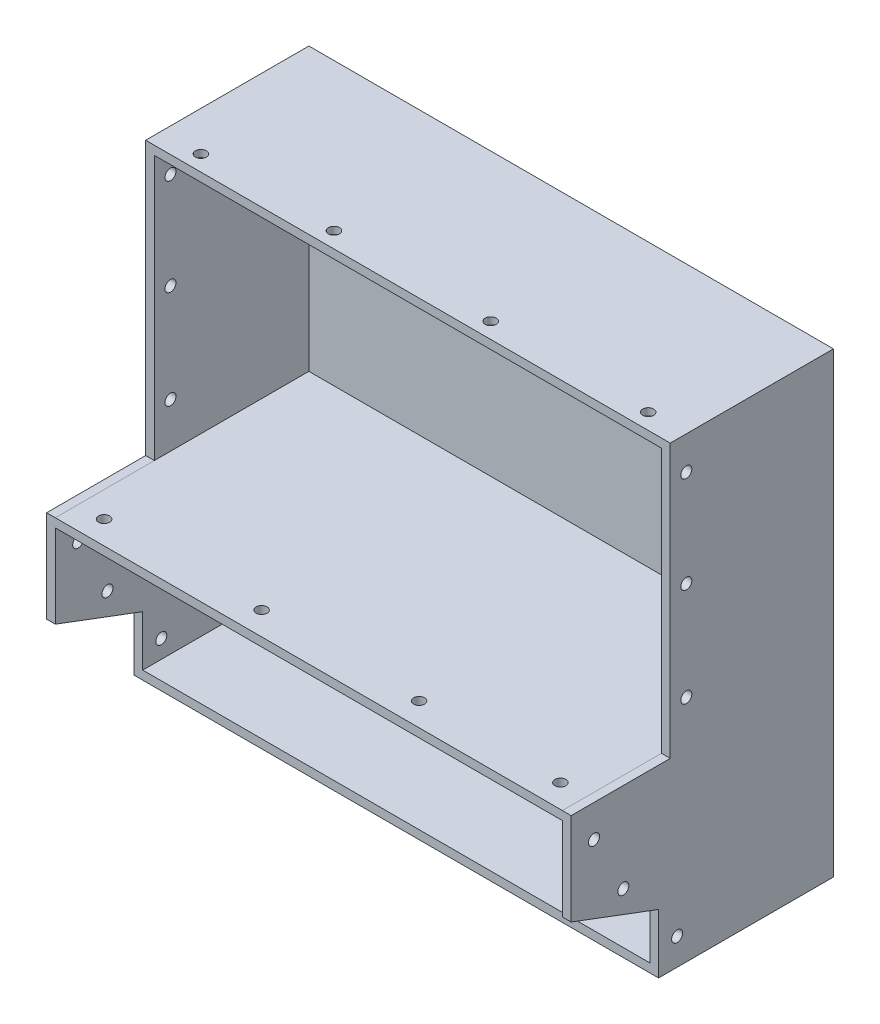
SolidWorks part; units mm, degrees
material "Custom Plastic"
ref_plane "X-Y Datum" through (0, 0, 0) normal (0, 0, 1) x (1, 0, 0)
ref_plane "X-Z Datum" through (0, 0, 0) normal (0, 1, 0) x (1, 0, 0)
ref_plane "Y-Z Datum" through (0, 0, 0) normal (1, 0, 0) x (0, 0, -1)
sketch "Sketch1" plane through (0, 0, 0) normal (0, 0, 1) x (1, 0, 0)
  line L1 (-95.25, -83.058) -> (95.25, -83.058)
  line L2 (-95.25, -83.058) -> (-95.25, 83.058)
  line L3 (-95.25, 83.058) -> (95.25, 83.058)
  line L4 (95.25, -83.058) -> (95.25, 83.058)
  line L5 (-95.25, -83.058) -> (95.25, 83.058) construction
  line L6 (-95.25, 83.058) -> (95.25, -83.058) construction
  point P0 (0, 0)
  dimension "D1" = 166.116
  dimension "D2" = 190.5
extrude "Boss-Extrude1" add sketch "Sketch1" along normal blind 95.25
sketch "Sketch3" plane through (0, 0, 95.25) normal (0, 0, 1) x (1, 0, 0)
  line L0 (-92.075, -49.9618) -> (92.075, -49.9618)
  line L1 (92.075, -61.8913) -> (95.25, -61.8913)
  line L2 (-92.075, -61.8913) -> (92.075, -61.8913)
  line L3 (95.25, -83.058) -> (95.25, 83.058) construction
  line L4 (-92.075, -61.8913) -> (-92.075, -79.883)
  line L5 (-95.25, -49.9618) -> (-95.25, -61.8913)
  line L6 (92.075, -61.8913) -> (92.075, -79.883)
  line L7 (-95.25, 83.058) -> (-95.25, -83.058) construction
  line L8 (-122.0928, 3.2687) -> (-122.1486, 3.2687)
  line L9 (92.075, -79.883) -> (76.2531, -79.883)
  line L13 (-95.25, 32.8917) -> (-92.075, 32.8917)
  line L15 (-122.0786, -16.0951) -> (-122.1486, -16.0951)
  line L17 (95.25, -49.9618) -> (92.075, -49.9618)
  line L18 (-92.075, -79.883) -> (76.2531, -79.883)
  line L21 (-92.075, -49.9618) -> (-95.25, -49.9618)
  line L23 (-81.0858, 79.883) -> (83.8833, 79.883)
  line L25 (-81.0858, 79.883) -> (-92.075, 79.883)
  line L26 (-92.075, 79.883) -> (-92.075, -16.0951)
  line L28 (95.25, 48.6627) -> (92.075, 48.6627)
  line L30 (83.8833, 79.883) -> (92.075, 79.883)
  line L31 (92.075, 79.883) -> (92.075, -16.0951)
  line L33 (-92.075, -16.0951) -> (92.075, -16.0951)
  line L34 (95.25, -49.9618) -> (95.25, -61.8913)
  line L35 (-95.25, -61.8913) -> (-92.075, -61.8913)
extrude "Cut-Extrude1" cut sketch "Sketch3" against normal blind 92.075 contours L23 region at (0, 31.8939, 95.25)
sketch "Sketch15" plane through (0, 0, 95.25) normal (0, 0, 1) x (1, 0, 0)
  line L1 (-95.25, 83.058) -> (-95.25, -83.058) construction
  line L3 (95.25, -83.058) -> (95.25, 83.058) construction
  line L4 (95.25, -16.1093) -> (95.25, 83.058)
  line L5 (95.25, 83.058) -> (-95.25, 83.058)
  line L6 (-95.25, 83.058) -> (-95.25, -16.1093)
  line L10 (95.25, -16.1093) -> (92.075, -16.0951)
  line L11 (92.075, -16.0951) -> (92.075, 79.883)
  line L12 (92.075, 79.883) -> (-92.075, 79.883)
  line L13 (-92.075, 79.883) -> (-92.075, -16.0951)
  line L14 (-92.075, -16.0951) -> (92.075, -16.0951) construction
  line L15 (-92.075, 79.883) -> (-92.075, -16.0951) construction
  line L16 (-95.25, -16.1093) -> (-92.075, -16.0951)
extrude "Cut-Extrude5" cut sketch "Sketch15" against normal blind 35.9842
sketch "Sketch17" plane through (0, 0, 95.25) normal (0, 0, 1) x (1, 0, 0)
  line L0 (-95.25, -49.5836) -> (-95.25, -83.058)
  line L2 (-95.25, -83.058) -> (95.25, -83.058)
  line L3 (-95.25, -16.1093) -> (-95.25, -83.058) construction
  line L4 (95.25, -83.058) -> (95.25, -16.1093) construction
  line L5 (95.25, -83.058) -> (95.25, -49.5836)
  line L6 (-95.25, -49.5836) -> (95.25, -49.5836)
extrude "Cut-Extrude6" cut sketch "Sketch17" against normal blind 31.75
sketch "Sketch18" plane through (-95.25, 0, 0) normal (-1, 0, 0) x (0, 0, 1)
  line L0 (63.5, -49.5836) -> (63.5, -61.5061)
  line L1 (63.5, -49.5836) -> (63.5, -83.058) construction
  line L2 (63.5, -61.5061) -> (95.25, -49.5836)
  line L3 (95.25, -49.5836) -> (63.5, -49.5836)
extrude "Boss-Extrude8" add sketch "Sketch18" against normal blind 190.5
sketch "Sketch19" plane through (0, 0, 95.25) normal (0, 0, 1) x (1, 0, 0)
  line L0 (-92.075, -19.2701) -> (-92.075, -49.5836)
  line L2 (95.25, -49.5836) -> (-95.25, -49.5836) construction
  line L4 (92.075, -19.2701) -> (92.075, -49.5836)
  line L6 (92.075, -49.5836) -> (-92.075, -49.5836)
  line L8 (-92.075, -19.2701) -> (92.075, -19.2701)
extrude "Cut-Extrude7" cut sketch "Sketch19" against normal blind 92.075
sketch "Sketch20" plane through (0, -74.8032, 28.0894) normal (0, -0.9362, 0.3515) x (1, 0, 0)
  line L2 (-92.075, -3.8019) -> (-92.075, 82.3961) construction
  line L4 (-92.075, 71.7396) -> (92.075, 71.7396) construction
  line L6 (-92.075, 71.7396) -> (92.075, 71.7396)
  line L12 (92.075, -3.8019) -> (92.075, 82.3961) construction
  line L13 (95.25, 71.7396) -> (92.075, 71.7396) construction
  line L15 (-92.075, 71.7396) -> (-92.075, 37.8249)
  line L16 (95.25, 37.8249) -> (-95.25, 37.8249) construction
  line L17 (92.075, 71.7396) -> (92.075, 37.8249)
  line L18 (92.075, 37.8249) -> (-92.075, 37.8249)
extrude "Cut-Extrude8" cut sketch "Sketch20" against normal blind 13.175
sketch "Sketch21" plane through (0, 0, 63.5) normal (0, 0, 1) x (1, 0, 0)
  line L0 (-92.075, -61.5061) -> (-92.075, -49.5836)
  line L2 (-92.075, -49.5836) -> (92.075, -49.5836)
  line L4 (92.075, -49.5836) -> (92.075, -61.5061)
  line L6 (-92.075, -61.5061) -> (-92.075, -79.883)
  line L7 (-92.075, -79.883) -> (92.075, -79.883)
  line L8 (92.075, -79.883) -> (92.075, -61.5061)
extrude "Cut-Extrude9" cut sketch "Sketch21" against normal blind 60.325
sketch "Sketch23" plane through (0, -83.058, 0) normal (0, -1, 0) x (1, 0, 0)
  circle A4 centre (-82.8492, 55.0007) radius 2
  circle A5 centre (-25.472, 55.0007) radius 2
  circle A6 centre (31.5236, 55.0007) radius 2
  circle A7 centre (82.8147, 55.0007) radius 2
extrude "Cut-Extrude10" cut sketch "Sketch23" against normal blind 2.54
sketch "Sketch24" plane through (0, 83.058, 0) normal (0, 1, 0) x (1, 0, 0)
  line L0 (81.5233, -53.5508) -> (-86.3243, -53.5508) construction
  line L1 (95.25, -59.2658) -> (-95.25, -59.2658) construction
  circle A0 centre (81.5233, -53.5508) radius 2
  circle A3 centre (24.3357, -53.5508) radius 2
  circle A4 centre (-32.5907, -53.5508) radius 2
  circle A7 centre (-80.8952, -53.5508) radius 2
  dimension "D1" = 5.715
extrude "Cut-Extrude11" cut sketch "Sketch24" against normal blind 2.54
sketch "Sketch25" plane through (95.25, 0, 0) normal (1, 0, 0) x (0, 0, -1)
  circle A0 centre (-53.4238, 70.993) radius 2
  circle A1 centre (-53.4238, 35.941) radius 2
  circle A4 centre (-53.4238, 0.889) radius 2 [skipped]
  circle A6 centre (-53.4238, 0.2178) radius 2
  dimension "D2" = 3
extrude "Cut-Extrude12" cut sketch "Sketch25" against normal through all
sketch "Sketch26" plane through (0, -16.0951, 0) normal (0, 1, 0) x (1, 0, 0)
  line L1 (92.075, -59.2658) -> (92.075, -95.25) construction
  line L2 (92.075, -63.7108) -> (-92.075, -63.7108)
  line L3 (-92.075, -59.2658) -> (-92.075, -95.25) construction
  line L5 (-92.075, -79.375) -> (92.075, -79.375)
sketch "Sketch27" plane through (0, -16.0951, 0) normal (0, 1, 0) x (1, 0, 0)
  circle A0 centre (82.9278, -86.8228) radius 2
  circle A8 centre (31.5919, -86.8228) radius 2
  circle A11 centre (-25.6023, -86.8228) radius 2
  circle A12 centre (-82.8005, -86.8228) radius 2
extrude "Cut-Extrude13" cut sketch "Sketch27" against normal blind 3.175
sketch "Sketch28" plane through (95.25, 0, 0) normal (1, 0, 0) x (0, 0, -1)
  circle A0 centre (-56.7612, -73.2851) radius 2
  circle A1 centre (-76.307, -48.5678) radius 2
  circle A2 centre (-86.9498, -27.7945) radius 2
extrude "Cut-Extrude15" cut sketch "Sketch28" against normal through all
